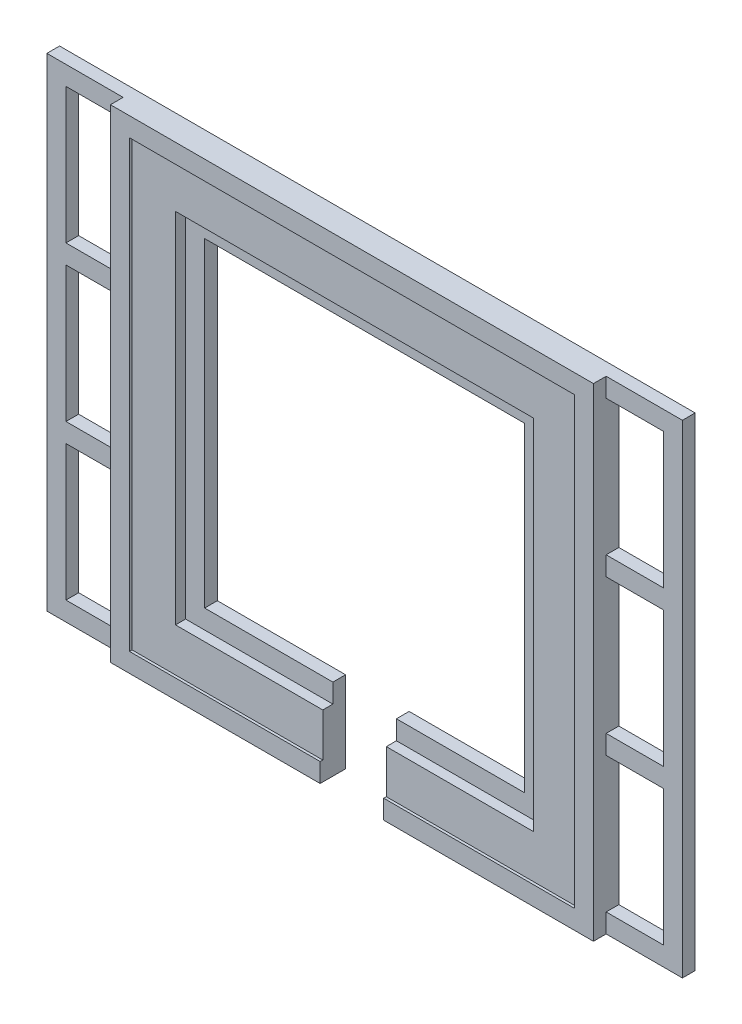
SolidWorks part; units mm, degrees
ref_plane "Front Plane" through (0, 0, 0) normal (0, 0, 1) x (1, 0, 0)
ref_plane "Top Plane" through (0, 0, 0) normal (0, 1, 0) x (1, 0, 0)
ref_plane "Right Plane" through (0, 0, 0) normal (1, 0, 0) x (0, 0, -1)
sketch "Sketch1" plane through (0, 0, 0) normal (0, 0, 1) x (1, 0, 0)
  line L0 (50, 76) -> (50, 0) construction
  line L1 (0, 0) -> (100, 0)
  line L2 (0, 0) -> (0, 76)
  line L3 (0, 76) -> (100, 76)
  line L4 (100, 0) -> (100, 76)
  line L5 (97, 3) -> (88, 3)
  line L6 (3, 73) -> (12, 73)
  line L7 (3, 73) -> (3, 51.6667)
  line L8 (3, 51.6667) -> (12, 51.6667)
  line L9 (12, 73) -> (12, 51.6667)
  line L10 (3, 48.6667) -> (12, 48.6667)
  line L11 (3, 48.6667) -> (3, 27.3333)
  line L12 (3, 27.3333) -> (12, 27.3333)
  line L13 (12, 48.6667) -> (12, 27.3333)
  line L14 (3, 24.3333) -> (12, 24.3333)
  line L15 (3, 24.3333) -> (3, 3)
  line L16 (3, 3) -> (12, 3)
  line L17 (12, 24.3333) -> (12, 3)
  line L18 (15, 73) -> (85, 73)
  line L19 (15, 73) -> (15, 3)
  line L20 (15, 3) -> (85, 3)
  line L21 (85, 73) -> (85, 3)
  line L22 (88, 24.3333) -> (88, 3)
  line L23 (97, 24.3333) -> (97, 3)
  line L24 (97, 24.3333) -> (88, 24.3333)
  line L25 (88, 48.6667) -> (88, 27.3333)
  line L26 (97, 48.6667) -> (97, 27.3333)
  line L27 (97, 48.6667) -> (88, 48.6667)
  line L28 (97, 51.6667) -> (88, 51.6667)
  line L29 (88, 73) -> (88, 51.6667)
  line L30 (97, 73) -> (97, 51.6667)
  line L31 (97, 73) -> (88, 73)
  line L32 (88, 27.3333) -> (97, 27.3333)
  line L33 (0, 38) -> (100, 38) construction
  line L34 (21.825, 66.175) -> (78.175, 66.175)
  line L35 (21.825, 66.175) -> (21.825, 9.825)
  line L36 (21.825, 9.825) -> (78.175, 9.825)
  line L37 (78.175, 66.175) -> (78.175, 9.825)
  line L38 (12, 51.6667) -> (12, 48.6667)
  line L39 (12, 27.3333) -> (12, 24.3333)
  line L40 (12, 73) -> (12, 76)
  line L41 (88, 73) -> (88, 76)
  line L42 (88, 51.6667) -> (88, 48.6667)
  line L43 (88, 27.3333) -> (88, 24.3333)
  line L44 (88, 3) -> (88, 0)
  line L45 (12, 3) -> (12, 0)
  line L46 (45, 12.825) -> (45, 0)
  line L47 (55, 12.825) -> (55, 0)
  line L49 (24.825, 63.175) -> (75.175, 63.175)
  line L50 (24.825, 63.175) -> (24.825, 12.825)
  line L51 (24.825, 12.825) -> (75.175, 12.825)
  line L52 (75.175, 63.175) -> (75.175, 12.825)
  point P41 (21.825, 38)
  point P42 (50, 66.175)
  dimension "D1" = 3
  dimension "D2" = 3
  dimension "D3" = 3
  dimension "D4" = 3
  dimension "D5" = 3
  dimension "D6" = 56.35
  dimension "D7" = 56.35
  dimension "D8" = 3
  dimension "D9" = 3
  dimension "D10" = 3
  dimension "D11" = 3
  dimension "D12" = 70
  dimension "D13" = 70
  dimension "D14" = 100
  dimension "D15" = 5
  dimension "D16" = 3
  dimension "D17" = 3
  dimension "D18" = 3
  dimension "D19" = 3
extrude "Boss-Extrude1" add sketch "Sketch1" along normal blind 2 contours L45 L16 L15 L14 L39 L12 L11 L10 L38 L8 L7 L6 L40 L3 L2 L1 | L20 L47 L1 L44 L22 L43 L25 L42 L29 L41 L3 L40 L9 L38 L13 L39 L17 L45 L46 L19 L18 L21 | L36 L47 L20 L21 L18 L19 L46 L35 L34 L37 | L37 L34 L35 L36 L49 L52 L51 L50 | L5 L44 L1 L4 L3 L41 L31 L30 L28 L42 L27 L26 L32 L43 L24 L23 region at (0.7694, 38, 0) region at (13.0748, 1.5, 0) region at (30, 3.9899, 0) region at (94, 75.2306, 0) region at (33.4125, 10.6219, 0)
extrude "Boss-Extrude2" add sketch "Sketch1<3>" along normal blind 3.59 contours L21 L18 L19 L20 L34 L37 L36 L35 region at (30, 3.9899, 0)
sketch "Sketch1<3>" plane through (0, 0, 0) normal (0, 0, 1) x (1, 0, 0) same geometry as "Sketch1"
extrude "Boss-Extrude3" add sketch "Sketch1<4>" along normal blind 4 contours L17 L45 L1 L44 L22 L43 L25 L42 L29 L41 L3 L40 L9 L38 L13 L39 L18 L21 L20 L19 region at (13.0748, 1.5, 0)
sketch "Sketch1<4>" plane through (0, 0, 0) normal (0, 0, 1) x (1, 0, 0) same geometry as "Sketch1"
